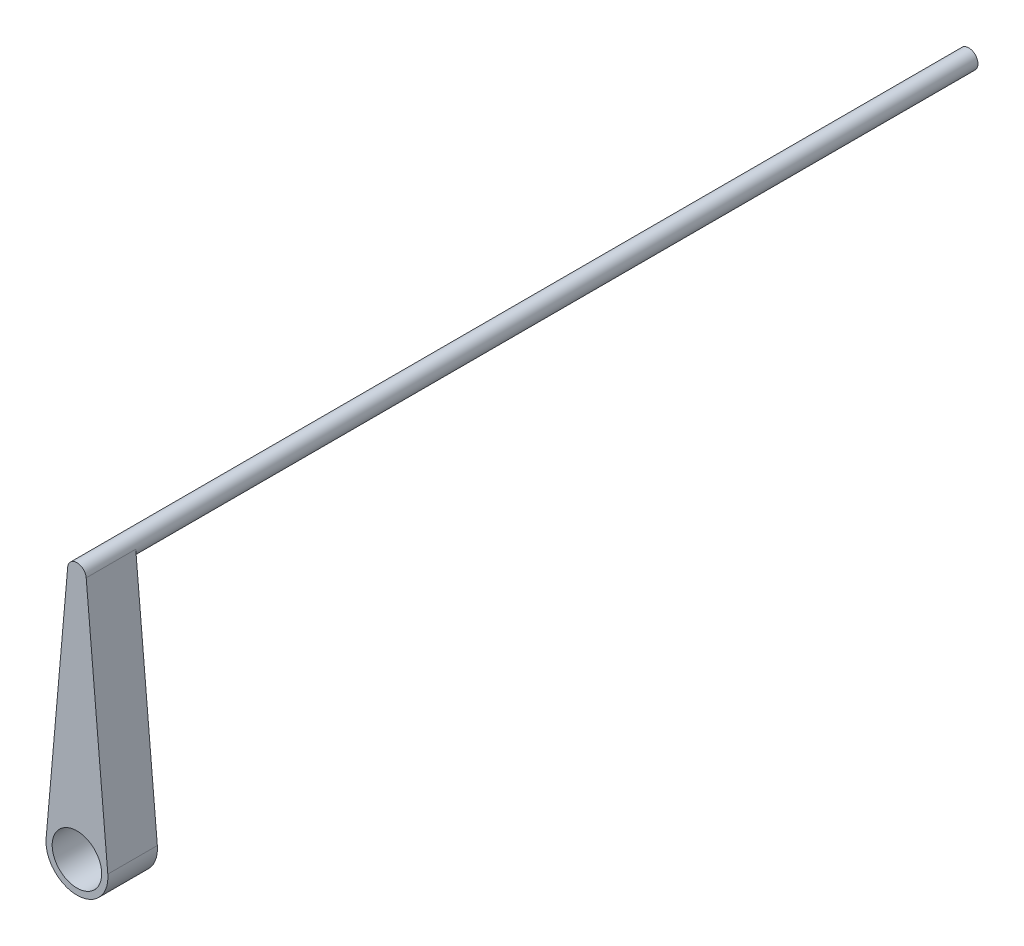
SolidWorks part; units mm, degrees
ref_plane "Ön Düzlem" through (0, 0, 0) normal (0, 0, 1) x (1, 0, 0)
ref_plane "Üst Düzlem" through (0, 0, 0) normal (0, 1, 0) x (1, 0, 0)
ref_plane "Sağ Düzlem" through (0, 0, 0) normal (1, 0, 0) x (0, 0, -1)
sketch "Çizim1" plane through (0, 0, 0) normal (0, 0, 1) x (1, 0, 0)
  line L0 (-2.4904, 0.2188) -> (-0.7471, 20.0656)
  line L1 (0, 20) -> (0, 0) construction
  line L2 (2.4904, 0.2188) -> (0.7471, 20.0656)
  circle A0 centre (0, 0) radius 2
  circle A1 centre (0, 0) radius 2.5
  circle A2 centre (0, 20) radius 0.75
  dimension "D1" = 4
  dimension "D2" = 5
  dimension "D3" = 1.5
  dimension "D4" = 20
extrude "Yükseklik-Ekstrüzyon1" add sketch "Çizim1" along normal blind 4 contours A1 A0 | A2 L1 A1 L2 | L1 A2 L0 A1 region at (-1.6409, 1.7913, 0) region at (-0.8738, 9.3053, 0) region at (0.8738, 9.3053, 0)
extrude "Yükseklik-Ekstrüzyon2" add sketch "Çizim1<3>" along normal blind 4 and the other way blind 68 contours A2 region at (0, 20, 0)
sketch "Çizim1<3>" plane through (0, 0, 0) normal (0, 0, 1) x (1, 0, 0) same geometry as "Çizim1"
